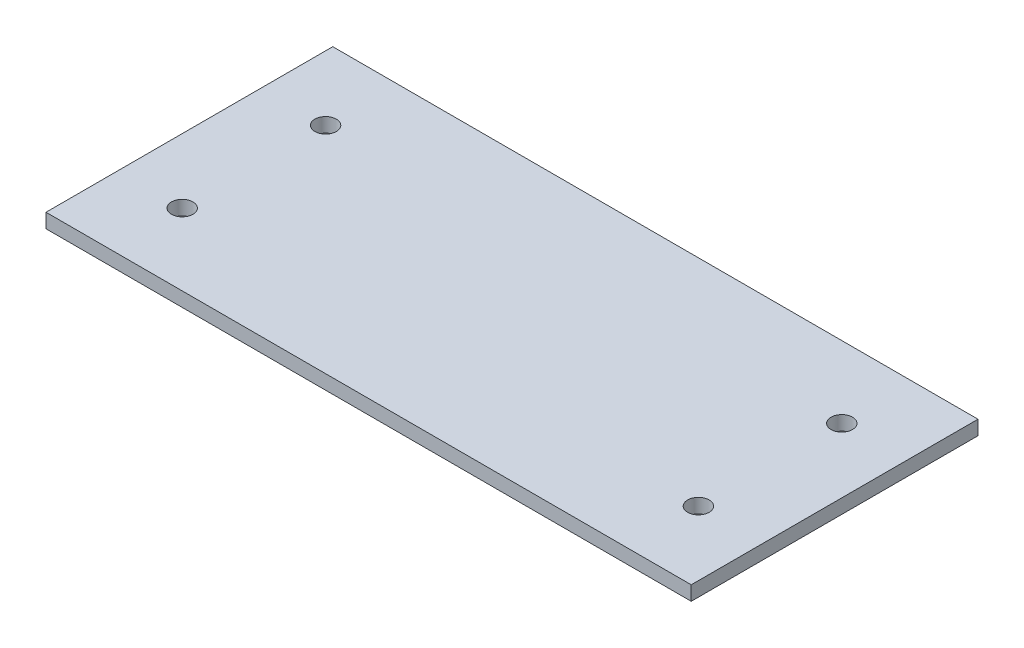
SolidWorks part; units mm, degrees
ref_plane "前视基准面" through (0, 0, 0) normal (0, 0, 1) x (1, 0, 0)
ref_plane "上视基准面" through (0, 0, 0) normal (0, 1, 0) x (1, 0, 0)
ref_plane "右视基准面" through (0, 0, 0) normal (1, 0, 0) x (0, 0, -1)
sketch "Sketch1" plane through (0, 0, 0) normal (0, 1, 0) x (1, 0, 0)
  line L1 (-45, 20) -> (45, 20)
  line L2 (-45, 20) -> (-45, -20)
  line L3 (-45, -20) -> (45, -20)
  line L4 (45, 20) -> (45, -20)
  line L5 (-45, 20) -> (45, -20) construction
  line L6 (-45, -20) -> (45, 20) construction
  line L11 (-36, -10) -> (36, 10) construction
  line L12 (-36, 10) -> (36, -10) construction
  circle A0 centre (36, 10) radius 1.5
  circle A1 centre (36, -10) radius 1.5
  circle A2 centre (-36, -10) radius 1.5
  circle A3 centre (-36, 10) radius 1.5
  point P0 (0, 0)
  point P6 (0, 0)
  dimension "D6" = 3
  dimension "D7" = 3
  dimension "D8" = 3
  dimension "D1" = 90
  dimension "D2" = 40
  dimension "D3" = 72
  dimension "D4" = 20
extrude "Boss-Extrude1" add sketch "Sketch1" along normal blind 2
